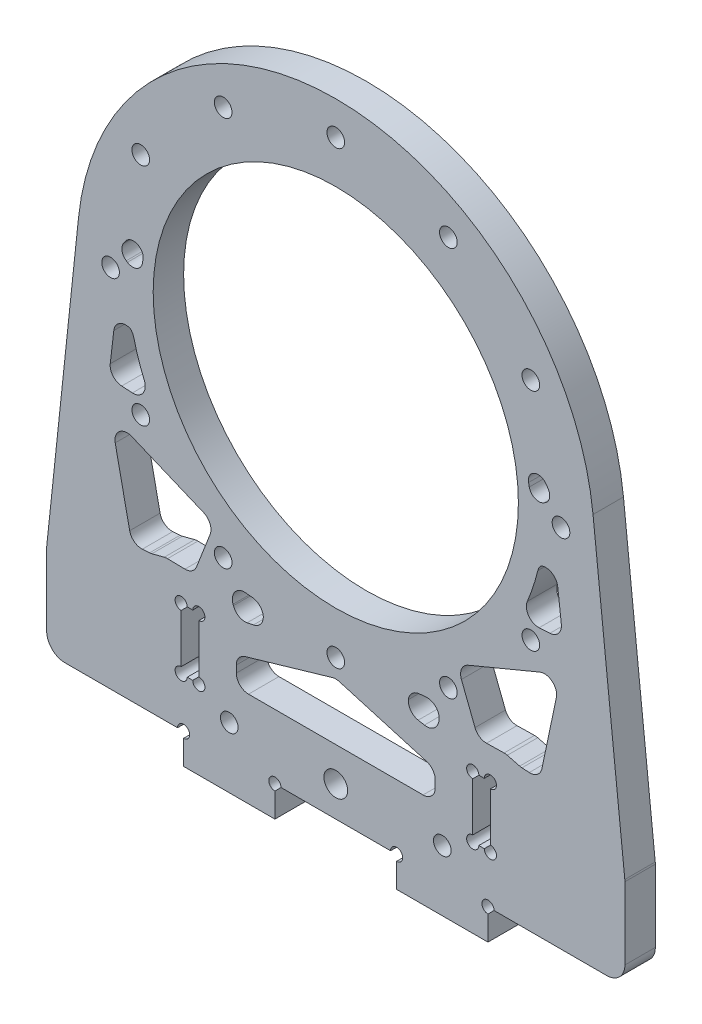
SolidWorks part; units mm, degrees
material "Thornel Mat VMA"
ref_plane "前视基准面" through (0, 0, 0) normal (0, 0, 1) x (1, 0, 0)
ref_plane "上视基准面" through (0, 0, 0) normal (0, 1, 0) x (1, 0, 0)
ref_plane "右视基准面" through (0, 0, 0) normal (1, 0, 0) x (0, 0, -1)
other "Configuration Table"
sketch "草图1" plane through (0, 0, 0) normal (0, 0, 1) x (1, 0, 0)
  line L0 (0, 0) -> (0, 60) construction
  line L1 (-42.264, 64.4731) -> (-47.5, 15)
  line L2 (-47.5, 15) -> (-47.5, 0)
  line L3 (-47.5, 0) -> (47.5, 0)
  line L4 (47.5, 15) -> (47.5, 0)
  line L5 (42.264, 64.4731) -> (47.5, 15)
  circle A0 centre (0, 60) radius 37 construction
  circle A1 centre (0, 60) radius 30
  circle A2 centre (0, 97) radius 1.45
  circle A3 centre (18.5, 92.0429) radius 1.45
  circle A4 centre (32.0429, 78.5) radius 1.45
  circle A5 centre (37, 60) radius 1.45
  circle A6 centre (32.0429, 41.5) radius 1.45
  circle A7 centre (18.5, 27.9571) radius 1.45
  circle A8 centre (0, 23) radius 1.45
  circle A9 centre (-18.5, 27.9571) radius 1.45
  circle A10 centre (-32.0429, 41.5) radius 1.45
  circle A11 centre (-37, 60) radius 1.45
  circle A12 centre (-32.0429, 78.5) radius 1.45
  circle A13 centre (-18.5, 92.0429) radius 1.45
  circle A14 centre (0, 60) radius 42.5 construction
  arc A15 (-42.264, 64.4731) -> (42.264, 64.4731) centre (0, 60) cw
  dimension "D1" = 74
  dimension "D2" = 60
  dimension "D4" = 2.9
  dimension "D6" = 85
  dimension "D7" = 15
  dimension "D3" = 60
  dimension "D8" = 95
  dimension "D5" = 12
extrude "凸台-拉伸1" add sketch "草图1" along normal blind 5
sketch "草图2" plane through (0, 0, 5) normal (0, 0, 1) x (1, 0, 0)
  line L0 (0, 0) -> (0, 102.5) construction
  line L1 (-47.5, 0) -> (47.5, 0) construction
  line L2 (-25, 0) -> (-10, 0)
  line L3 (-25, 0) -> (-25, -5)
  line L4 (-25, -5) -> (-10, -5)
  line L5 (-10, 0) -> (-10, -5)
  line L6 (25, -5) -> (10, -5)
  line L7 (10, 0) -> (10, -5)
  line L8 (25, 0) -> (10, 0)
  line L9 (25, 0) -> (25, -5)
  arc A0 (42.264, 64.4731) -> (-42.264, 64.4731) centre (0, 60) ccw construction
  dimension "D1" = 5
  dimension "D2" = 50
  dimension "D3" = 15
extrude "凸台-拉伸2" add sketch "草图2" against normal blind 5
sketch "草图3" plane through (0, 0, 5) normal (0, 0, 1) x (1, 0, 0)
  circle A0 centre (-25, 0) radius 1
  circle A1 centre (-10, 0) radius 1
  circle A2 centre (10, 0) radius 1
  circle A3 centre (25, 0) radius 1
  dimension "D1" = 2
extrude "切除-拉伸1" cut sketch "草图3" against normal through all
sketch "草图4" plane through (0, 0, 5) normal (0, 0, 1) x (1, 0, 0)
  line L0 (0, 0) -> (0, 102.5) construction
  line L8 (-47.5, 15) -> (-47.5, 0) construction
  line L9 (47.5, 0) -> (47.5, 15) construction
  line L10 (-47.5, 5) -> (47.5, 5) construction
  line L15 (26, 0) -> (47.5, 0) construction
  line L16 (-17.5, -5) -> (-17.5, 5) construction
  line L17 (-25, -5) -> (-10, -5) construction
  line L18 (17.5, -5) -> (17.5, 5) construction
  line L19 (10, -5) -> (25, -5) construction
  arc A0 (42.264, 64.4731) -> (-42.264, 64.4731) centre (0, 60) ccw construction
  circle A1 centre (0, 5) radius 1.95
  circle A2 centre (0, 60) radius 46 construction
  circle A3 centre (-17.5, 5) radius 1.45
  circle A4 centre (17.5, 5) radius 1.45
  circle A5 centre (0, 5) radius 1.45 construction
  circle A6 centre (-4, 5) radius 1.95 construction
  circle A7 centre (4, 5) radius 1.95 construction
  dimension "D6" = 92
  dimension "D5" = 2.9
  dimension "D1" = 8
  dimension "D2" = 3.9
  dimension "D3" = 3.9
  dimension "D4" = 5
extrude "切除-拉伸2" cut sketch "草图4" against normal through all
fillet "圆角1" radius 3 4 edges at (47.5, 15, 2.5) (47.5, 0, 2.5) (-47.5, 0, 2.5) (-47.5, 15, 2.5)
sketch "草图5" plane through (0, 0, 5) normal (0, 0, 1) x (1, 0, 0)
  line L2 (22.5, 0) -> (22.5, 18) construction
  line L3 (26, 0) -> (44.5, 0) construction
  line L4 (47.5, 3) -> (47.5, 14.8417) construction
  line L5 (0, 0) -> (0, 23) construction
  line L6 (22.5, 18) -> (25.4, 18)
  line L7 (22.5, 18) -> (22.5, 8)
  line L8 (22.5, 8) -> (25.4, 8)
  line L9 (25.4, 18) -> (25.4, 8)
  line L10 (-25.4, 18) -> (-25.4, 8)
  line L11 (-22.5, 8) -> (-25.4, 8)
  line L12 (-22.5, 18) -> (-22.5, 8)
  line L13 (-22.5, 18) -> (-25.4, 18)
  dimension "D1" = 25
  dimension "D2" = 10
  dimension "D3" = 2.9
  dimension "D4" = 8
extrude "切除-拉伸3" cut sketch "草图5" against normal through all
sketch "草图6" plane through (0, 0, 5) normal (0, 0, 1) x (1, 0, 0)
  circle A0 centre (-25.4, 18) radius 1
  circle A1 centre (-22.5, 18) radius 1
  circle A2 centre (-22.5, 8) radius 1
  circle A3 centre (-25.4, 8) radius 1
  circle A4 centre (22.5, 8) radius 1
  circle A5 centre (25.4, 8) radius 1
  circle A6 centre (25.4, 18) radius 1
  circle A7 centre (22.5, 18) radius 1
  dimension "D1" = 2
extrude "切除-拉伸4" cut sketch "草图6" against normal through all
sketch "草图7" plane through (0, 0, 5) normal (0, 0, 1) x (1, 0, 0)
  line L0 (-41.7719, 67.8333) -> (-34.8185, 75.9419) construction
  line L1 (-34.8185, 75.9419) -> (-34.4646, 78.7998) construction
  line L2 (-32.5275, 80.8916) -> (-24.57, 82.5038) construction
  line L3 (-19.9001, 86.7224) -> (-21.4264, 90.9984) construction
  line L4 (-18.5, 95.1501) -> (-4.3217, 94.6049) construction
  line L5 (-4.3217, 94.6049) -> (-2.5884, 98.2357) construction
  line L6 (2.4119, 98.5524) -> (5.5323, 93.7042) construction
  line L7 (0, 60) -> (0, 97) construction
  line L8 (4.3217, 94.6049) -> (2.5884, 98.2357) construction
  line L9 (18.5, 95.1501) -> (4.3217, 94.6049) construction
  line L10 (19.9001, 86.7224) -> (21.4264, 90.9984) construction
  line L11 (32.5275, 80.8916) -> (24.57, 82.5038) construction
  line L12 (34.8185, 75.9419) -> (34.4646, 78.7998) construction
  line L13 (41.7719, 67.8333) -> (34.8185, 75.9419) construction
  arc A0 (42.264, 64.4731) -> (-42.264, 64.4731) centre (0, 60) ccw construction
  circle A1 centre (-32.0429, 78.5) radius 2.4402 construction
  circle A2 centre (0, 60) radius 33.3182 construction
  arc A3 (-24.57, 82.5038) -> (-19.9001, 86.7224) centre (0, 60) cw construction
  circle A4 centre (-18.5, 92.0429) radius 3.1072 construction
  arc A5 (-21.4264, 90.9984) -> (-18.5, 95.1501) centre (-18.5, 92.0429) cw construction
  circle A6 centre (0, 97) radius 2.8683 construction
  arc A7 (-2.5884, 98.2357) -> (2.4119, 98.5524) centre (0, 97) cw construction
  circle A8 centre (18.5, 92.0429) radius 3.1072 construction
  circle A9 centre (32.0429, 78.5) radius 2.4402 construction
  arc A10 (21.4264, 90.9984) -> (18.5, 95.1501) centre (18.5, 92.0429) ccw construction
  arc A11 (24.57, 82.5038) -> (19.9001, 86.7224) centre (0, 60) ccw construction
  arc A12 (-41.7719, 67.8333) -> (41.7719, 67.8333) centre (0, 60) cw construction
  arc A13 (34.4646, 78.7998) -> (32.5275, 80.8916) centre (32.0429, 78.5) ccw construction
  arc A14 (-34.4646, 78.7998) -> (-32.5275, 80.8916) centre (-32.0429, 78.5) cw construction
  arc A15 (-2.5884, 98.2357) -> (2.5884, 98.2357) centre (0, 97) cw construction
sketch "草图8" plane through (0, 0, 5) normal (0, 0, 1) x (1, 0, 0)
  line L0 (0, 0) -> (0, 60) construction
  line L1 (0, 20.0251) -> (-16.3396, 15.2594)
  line L2 (-16.3396, 15.2594) -> (-16.3396, 10.6135)
  line L3 (0, 20.0251) -> (16.3396, 15.2594)
  line L4 (16.3396, 15.2594) -> (16.3396, 10.6135)
  line L5 (-16.3396, 10.6135) -> (16.3396, 10.6135)
  line L6 (-30.1095, 71.5834) -> (-35.7829, 63.1271)
  line L7 (-35.7829, 63.1271) -> (-32.249, 60.8315)
  line L8 (-32.249, 60.8315) -> (-30.1095, 71.5834)
  line L12 (-33.3679, 52.7219) -> (-36.0963, 54.4652)
  line L13 (-36.0963, 54.4652) -> (-37.3047, 44.1496)
  line L14 (-37.3047, 44.1496) -> (-30.0411, 43.7545)
  line L15 (-37.0221, 39.1376) -> (-19.9294, 32.0173)
  line L16 (-19.9294, 32.0173) -> (-21.1733, 29.0949) construction
  line L17 (-17.9356, 25.107) -> (-12.0691, 24.5278)
  line L18 (-12.0691, 24.5278) -> (-11.7421, 21.1952)
  line L19 (-11.7421, 21.1952) -> (-16.2419, 20.3492)
  line L20 (-21.4742, 23.131) -> (-27.9177, 23.2439) construction
  line L21 (-27.9177, 23.2439) -> (-30.4, 22.6077)
  line L22 (-30.4, 22.6077) -> (-33.508, 22.4146)
  line L23 (-33.508, 22.4146) -> (-37.0221, 39.1376)
  line L24 (35.7829, 63.1271) -> (32.249, 60.8315)
  line L25 (30.1095, 71.5834) -> (35.7829, 63.1271)
  line L26 (32.249, 60.8315) -> (30.1095, 71.5834)
  line L27 (36.0963, 54.4652) -> (37.3047, 44.1496)
  line L28 (33.3679, 52.7219) -> (36.0963, 54.4652)
  line L29 (37.3047, 44.1496) -> (30.0411, 43.7545)
  line L30 (30.4, 22.6077) -> (33.508, 22.4146) construction
  line L31 (27.9177, 23.2439) -> (30.4, 22.6077) construction
  line L32 (21.4742, 23.131) -> (27.9177, 23.2439) construction
  line L33 (11.7421, 21.1952) -> (16.2419, 20.3492) construction
  line L34 (12.0691, 24.5278) -> (11.7421, 21.1952) construction
  line L35 (17.9356, 25.107) -> (12.0691, 24.5278) construction
  line L36 (19.9294, 32.0173) -> (21.1733, 29.0949) construction
  line L37 (37.0221, 39.1376) -> (19.9294, 32.0173) construction
  line L38 (33.508, 22.4146) -> (37.0221, 39.1376) construction
  line L39 (-47.5, 14.8417) -> (-47.5, 3) construction
  line L40 (-19.9294, 32.0173) -> (-23.3814, 23.1644)
  line L41 (-47.5, 30.1013) -> (-47.5, 3) construction
  line L42 (-47.5, 30.1013) -> (-46.294, 26.3949) construction
  line L43 (-42.264, 64.4731) -> (-47.4833, 15.1574) construction
  line L44 (-46.294, 26.3949) -> (-45.0646, 23.8642) construction
  line L45 (-44.5, 0) -> (-26, 0) construction
  line L46 (-37.0221, 0) -> (-44.5, 0) construction
  line L47 (-23.3814, 23.1644) -> (-27.9177, 23.2439)
  line L48 (46.294, 26.3949) -> (45.0646, 23.8642) construction
  line L49 (47.5, 30.1013) -> (46.294, 26.3949) construction
  line L50 (47.5, 30.1013) -> (47.5, 3) construction
  line L51 (37.0221, 0) -> (44.5, 0) construction
  line L52 (-16.2419, 20.3492) -> (-17.9356, 25.107)
  line L53 (11.7421, 21.1952) -> (16.2419, 20.3492)
  line L54 (12.0691, 24.5278) -> (11.7421, 21.1952)
  line L55 (17.9356, 25.107) -> (12.0691, 24.5278)
  line L56 (16.2419, 20.3492) -> (17.9356, 25.107)
  line L57 (19.9294, 32.0173) -> (23.3814, 23.1644)
  line L58 (37.0221, 39.1376) -> (19.9294, 32.0173)
  line L59 (33.508, 22.4146) -> (37.0221, 39.1376)
  line L60 (30.4, 22.6077) -> (33.508, 22.4146)
  line L61 (27.9177, 23.2439) -> (30.4, 22.6077)
  line L62 (23.3814, 23.1644) -> (27.9177, 23.2439)
  arc A0 (-33.3679, 52.7219) -> (-30.0411, 43.7545) centre (0, 60) ccw
  arc A1 (-21.1733, 29.0949) -> (-17.9356, 25.107) centre (-18.5, 27.9571) ccw construction
  arc A2 (-16.2419, 20.3492) -> (-21.4742, 23.131) centre (-22.6118, 14.6797) ccw construction
  arc A3 (33.3679, 52.7219) -> (30.0411, 43.7545) centre (0, 60) cw
  arc A4 (16.2419, 20.3492) -> (21.4742, 23.131) centre (22.6118, 14.6797) cw construction
  arc A5 (21.1733, 29.0949) -> (17.9356, 25.107) centre (18.5, 27.9571) cw construction
  arc A6 (-47.5, 3) -> (-44.5, 0) centre (-44.5, 3) ccw construction
  arc A7 (-47.5, 3) -> (-44.5, 0) centre (-44.5, 3) ccw construction
  arc A8 (-45.0646, 23.8642) -> (-37.0221, 0) centre (-11.0527, 22.0393) ccw construction
  arc A9 (45.0646, 23.8642) -> (37.0221, 0) centre (11.0527, 22.0393) cw construction
  arc A10 (47.5, 3) -> (44.5, 0) centre (44.5, 3) cw construction
extrude "切除-拉伸8" cut sketch "草图8" against normal through all contours A8 L44 L42 L41 A7 L46 | A2 L19 L18 L17 A1 L16 L15 L23 L22 L21 L20 | L5 L0 L1 L2 | L0 L5 L4 L3 | L36 A5 L35 L34 L33 A4 L32 L31 L30 L38 L37 | A10 L50 L49 L48 A9 L51 | L28 A3 L29 L27 | L26 L24 L25 | A0 L12 L13 L14 | L7 L8 L6 | L52 L19 L18 L17 | L53 L56 L55 L54 | L57 L62 L61 L60 L59 L58 | L23 L15 L16 A1 L17 L18 L19 A2 L20 L21 L22 | L5 L4 L3 L1 L2 | L30 L38 L37 L36 A5 L35 L34 L33 A4 L32 L31 | A9 L51 A10 L50 L49 L48 region at (0, 14.2625, 5) region at (-32.7138, 65.1807, 5) region at (-34.3346, 48.0154, 5) region at (-29.0313, 29.9108, 5) region at (-14.6684, 22.8561, 5) region at (32.7138, 65.1807, 5) region at (34.3346, 48.0154, 5) region at (14.6684, 22.8561, 5) region at (29.0313, 29.9108, 5)
fillet "圆角2" radius 2 33 edges at (-37.3047, 44.1496, 2.5) (-36.0963, 54.4652, 2.5) (-33.3679, 52.7219, 2.5) (-30.0411, 43.7545, 2.5) (37.3047, 44.1496, 2.5) (30.0411, 43.7545, 2.5) (33.3679, 52.7219, 2.5) (36.0963, 54.4652, 2.5) (-30.4, 22.6077, 2.5) (-33.508, 22.4146, 2.5) (-12.0691, 24.5278, 2.5) (-11.7421, 21.1952, 2.5) (-16.3396, 15.2594, 2.5) (0, 20.0251, 2.5) (16.3396, 15.2594, 2.5) (16.3396, 10.6135, 2.5) (-16.3396, 10.6135, 2.5) (-37.0221, 39.1376, 2.5) (-23.3814, 23.1644, 2.5) (-27.9177, 23.2439, 2.5) (-19.9294, 32.0173, 2.5) (-16.2419, 20.3492, 2.5) (19.9294, 32.0173, 2.5) (37.0221, 39.1376, 2.5) (33.508, 22.4146, 2.5) (30.4, 22.6077, 2.5) (27.9177, 23.2439, 2.5) (23.3814, 23.1644, 2.5) (11.7421, 21.1952, 2.5) (12.0691, 24.5278, 2.5) (17.9356, 25.107, 2.5) (16.2419, 20.3492, 2.5) (-17.9356, 25.107, 2.5)
fillet "圆角3" radius 1.6 6 edges at (35.7829, 63.1271, 2.5) (32.249, 60.8315, 2.5) (30.1095, 71.5834, 2.5) (-30.1095, 71.5834, 2.5) (-35.7829, 63.1271, 2.5) (-32.249, 60.8315, 2.5)
